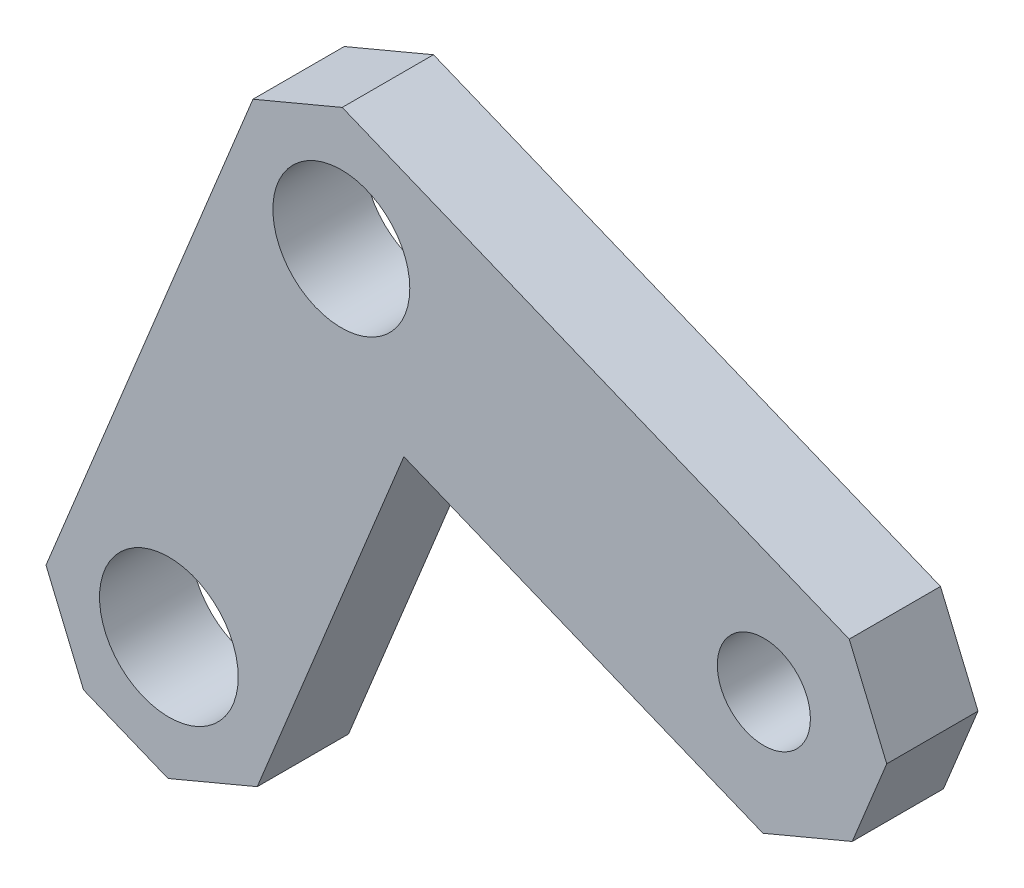
SolidWorks part; units mm, degrees
ref_plane "前基準面" through (0, 0, 0) normal (0, 0, 1) x (1, 0, 0)
ref_plane "上基準面" through (0, 0, 0) normal (0, 1, 0) x (1, 0, 0)
ref_plane "右基準面" through (0, 0, 0) normal (1, 0, 0) x (0, 0, -1)
sketch "草圖1" plane through (0, 0, 0) normal (0, 0, 1) x (1, 0, 0)
  line L0 (-42.6847, 14.9509) -> (26.7532, -13.3931)
  line L5 (26.7532, -13.3931) -> (17.3052, -36.5391)
  line L6 (17.3052, -36.5391) -> (-28.9867, -17.6431)
  line L7 (-28.9867, -17.6431) -> (-47.8827, -63.935)
  line L8 (-47.8827, -63.935) -> (-71.0287, -54.487)
  line L9 (-71.0287, -54.487) -> (-42.6847, 14.9509)
  line L10 (22.0292, -24.9661) -> (-47.4087, 3.3779) construction
  line L11 (-59.4557, -59.211) -> (-31.1117, 10.2269) construction
  circle A0 centre (10.4562, -20.2421) radius 5.1
  circle A1 centre (-35.8357, -1.3461) radius 7.5
  circle A2 centre (-54.7317, -47.638) radius 7.6
  point P12 (-35.8357, -1.3461)
  dimension "D5" = 10.2
  dimension "D8" = 15
  dimension "D9" = 15.2
  dimension "D1" = 25
  dimension "D2" = 25
  dimension "D3" = 75
  dimension "D4" = 75
  dimension "D6" = 12.5
  dimension "D7" = 12.5
  dimension "D10" = 12.5
extrude "填料-伸長1" add sketch "草圖1" against normal blind 10
chamfer "導角1" distance 7.5 angle 45 5 edges at (-47.8827, -63.935, -5) (17.3052, -36.5391, -5) (26.7532, -13.3931, -5) (-71.0287, -54.487, -5) (-42.6847, 14.9509, -5)
